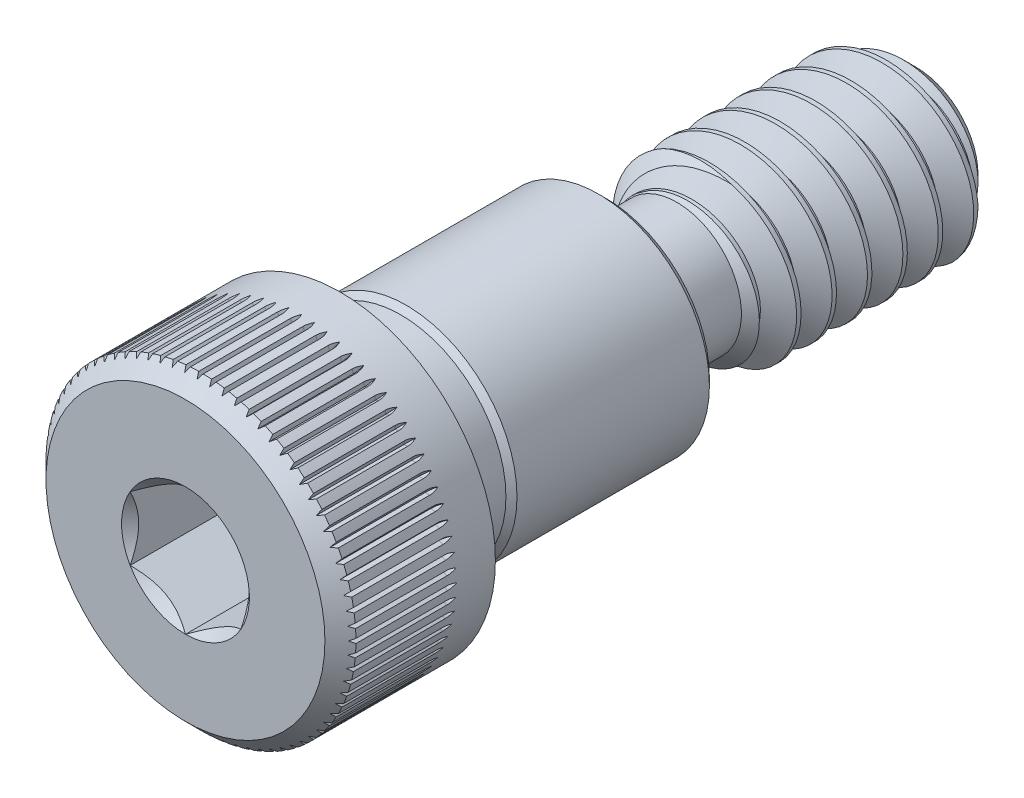
SolidWorks part; units mm, degrees
ref_plane "Front Plane" through (0, 0, 0) normal (0, 0, 1) x (1, 0, 0)
ref_plane "Top Plane" through (0, 0, 0) normal (0, 1, 0) x (1, 0, 0)
ref_plane "Right Plane" through (0, 0, 0) normal (1, 0, 0) x (0, 0, -1)
sketch "Sketch2" plane through (0, 0, 0) normal (1, 0, 0) x (0, 0, -1)
  line L0 (-13.0969, 0) -> (13.0969, 0) construction
  line L1 (-13.0969, 0) -> (-13.0969, 5.5563)
  line L2 (-13.0969, 5.5563) -> (-7.5406, 5.5563)
  line L3 (-7.5406, 5.5563) -> (-7.5406, 3.9688)
  line L4 (-7.5406, 3.9688) -> (1.9844, 3.9688)
  line L5 (1.9844, 3.175) -> (13.0969, 3.175)
  line L6 (13.0969, 3.175) -> (13.0969, 0)
  line L7 (13.0175, 3.3125) -> (13.6525, 2.2126) construction
  line L8 (13.6525, 2.2126) -> (14.2875, 3.3125) construction
  line L9 (14.2875, 3.3125) -> (13.0175, 3.3125) construction
  line L10 (13.0969, 3.175) -> (14.2081, 3.175) construction
  line L11 (13.6525, 3.3125) -> (13.6525, 3.175) construction
  line L12 (13.6525, 3.175) -> (13.6525, 2.3501) construction
  line L13 (13.6525, 2.3501) -> (13.6525, 2.2126) construction
  line L14 (13.5731, 2.3501) -> (13.7319, 2.3501)
  line L15 (13.0572, 3.2437) -> (14.2478, 3.2437)
  line L16 (13.7319, 2.3501) -> (14.2478, 3.2437)
  line L17 (13.5731, 2.3501) -> (13.0572, 3.2437)
  line L18 (13.0969, 0) -> (13.0969, -3.175) construction
  line L19 (1.9844, -3.9688) -> (1.9844, 0) construction
  line L20 (1.9844, 0) -> (1.9844, 3.9688) construction
  line L21 (-13.0969, 0) -> (-13.0969, -5.5563) construction
  point P11 (-5.1784, 3.9688)
  point P12 (9.9219, -3.175)
  point P22 (13.6525, 3.2437)
  point P23 (1.4287, 0)
  point P25 (-1.4287, 0)
  point P26 (-7.5406, -5.5563)
  point P29 (1.9844, -3.9688)
  dimension "Head Height" = 5.5562
  dimension "Shoulder Diameter" = 7.9375
  dimension "Screw Size Decimal Equivalent" = 6.35
  dimension "Thread Length" = 11.1125
  dimension "Head Diameter" = 11.1125
  dimension "Undercut Length" = 2.3622
  dimension "Pitch" = 1.27
  dimension "D2" = 0.1588
  dimension "D1" = 3.175
  dimension "D3" = 11.6681
  dimension "D4" = 11.6681
  dimension "Shoulder Length" = 9.525
sketch "Sketch3" plane through (0, 0, 0) normal (0, 0, 1) x (1, 0, 0)
  line L1 (0, 2.2914) -> (-1.9844, 1.1457)
  line L2 (-1.9844, 1.1457) -> (-1.9844, -1.1457)
  line L3 (-1.9844, -1.1457) -> (0, -2.2914)
  line L4 (0, -2.2914) -> (1.9844, -1.1457)
  line L5 (1.9844, -1.1457) -> (1.9844, 1.1457)
  line L6 (1.9844, 1.1457) -> (0, 2.2914)
  circle A0 centre (0, 0) radius 1.9844 construction
  dimension "Drive Size" = 3.9688
sketch "Sketch4" plane through (0, 0, 0) normal (1, 0, 0) x (0, 0, -1)
  line L0 (-7.5406, 5.5563) -> (-12.5412, 5.5562)
  line L1 (-12.5412, 5.5562) -> (-13.0969, 5.0006)
  line L2 (-7.5406, 5.5563) -> (-7.5406, 3.9688)
  line L3 (-7.5406, 3.9688) -> (-7.3422, 3.7703)
  line L4 (-7.3422, 3.7703) -> (-5.3769, 3.7703)
  line L5 (-5.3769, 3.7703) -> (-5.1784, 3.9688)
  line L6 (-7.5406, 3.9688) -> (1.9844, 3.9688) construction
  line L7 (-13.0969, 0) -> (13.0969, 0) construction
  line L8 (-5.1784, 3.9688) -> (1.7198, 3.9688)
  line L9 (1.7198, 3.9688) -> (1.9844, 3.7042)
  line L10 (1.9844, 3.7042) -> (1.9844, 0)
  line L11 (1.9844, 3.9688) -> (1.9844, 3.7042) construction
  line L12 (1.9844, 3.7042) -> (1.9844, 3.4396) construction
  line L13 (1.9844, 3.4396) -> (1.9844, 3.175) construction
  line L14 (-13.0969, 5.0006) -> (-13.0969, 0)
  line L15 (-13.0969, 5.5563) -> (-7.5406, 5.5563) construction
  line L16 (-13.0969, 0) -> (1.9844, 0)
  dimension "D1" = 45
  dimension "D2" = 7.5406
  dimension "D3" = 45
  dimension "D4" = 45
  dimension "D5" = 10.0012
revolve "Revolve1" add sketch "Sketch4" angle 360 about L16
sketch "Sketch5" plane through (0, 0, 13.0969) normal (0, 0, 1) x (1, 0, 0)
  line L0 (1.9844, 1.1457) -> (0, 2.2914) construction
  line L1 (1.9844, -1.1457) -> (1.9844, 1.1457) construction
  line L2 (0, -2.2914) -> (1.9844, -1.1457) construction
  line L3 (-1.9844, -1.1457) -> (0, -2.2914) construction
  line L4 (-1.9844, 1.1457) -> (-1.9844, -1.1457) construction
  line L5 (0, 2.2914) -> (-1.9844, 1.1457) construction
  line L6 (1.9844, 1.1457) -> (0, 2.2914)
  line L7 (1.9844, -1.1457) -> (1.9844, 1.1457)
  line L8 (0, -2.2914) -> (1.9844, -1.1457)
  line L9 (-1.9844, -1.1457) -> (0, -2.2914)
  line L10 (-1.9844, 1.1457) -> (-1.9844, -1.1457)
  line L11 (0, 2.2914) -> (-1.9844, 1.1457)
extrude "Cut-Extrude1" cut sketch "Sketch5" against normal blind 4.1672
sketch "Sketch6" plane through (0, 0, 13.0969) normal (0, 0, 1) x (1, 0, 0)
  circle A0 centre (0, 0) radius 2.2914
extrude "Cut-Extrude4" cut sketch "Sketch6" against normal blind 4.1672 draft 45
sketch "Sketch7" plane through (0, 0, 0) normal (1, 0, 0) x (0, 0, -1)
  line L0 (1.9844, 3.175) -> (12.1444, 3.175)
  line L1 (1.9844, 3.175) -> (13.0969, 3.175) construction
  line L2 (12.1444, 3.175) -> (13.0969, 2.2225)
  line L3 (13.0969, 3.175) -> (13.0969, 0) construction
  line L4 (13.0969, 2.2225) -> (13.0969, 0)
  line L5 (13.0969, 0) -> (1.9844, 0)
  line L6 (1.9844, -3.7042) -> (1.9844, 3.7042) construction
  line L7 (1.9844, 0) -> (1.9844, 3.175)
  dimension "D1" = 45
  dimension "D2" = 0.9525
revolve "Revolve2" add sketch "Sketch7" angle 360 about L5
sketch "Sketch10" plane through (0, 0, 0) normal (1, 0, 0) x (0, 0, -1)
  line L0 (2.848, 2.3114) -> (4.5244, 2.3114)
  line L1 (4.5244, 2.3114) -> (6.1817, 3.9688)
  line L2 (6.1817, 3.9688) -> (1.9844, 3.9688)
  line L3 (1.9844, 3.9688) -> (1.9844, 3.175)
  line L4 (1.9844, -3.7042) -> (1.9844, 3.7042) construction
  line L5 (13.0969, 0) -> (1.9844, 0) construction
  line L6 (-13.0969, 0) -> (13.0969, 0) construction
  arc A0 (1.9844, 3.175) -> (2.848, 2.3114) centre (2.848, 3.175) ccw
  dimension "Flat OD" = 4.6228
  dimension "Flat" = 2.54
  dimension "D3" = 45
revolve "Cut-Revolve1" cut sketch "Sketch10" angle 360 about L5
sketch "Sketch8" plane through (0, 0, -13.0969) normal (0, 0, -1) x (-1, 0, 0)
  circle A0 centre (0, 0) radius 3.175 construction
  circle A1 centre (0, 0) radius 3.175
curve "Helix/Spiral1" pitch 1.27 height 12.3825 radius 3.175 centre (0, 0, -13.0969) axis (0, 0, 1) start towards (0, 1, 0)
sketch "Sketch9" plane through (0, 0, 0) normal (1, 0, 0) x (0, 0, -1)
  line L0 (13.5731, 2.3501) -> (13.7319, 2.3501) construction
  line L1 (13.7319, 2.3501) -> (14.2478, 3.2437) construction
  line L2 (13.0572, 3.2437) -> (14.2478, 3.2437) construction
  line L3 (13.5731, 2.3501) -> (13.0572, 3.2437) construction
  line L4 (13.5731, 2.3501) -> (13.7319, 2.3501)
  line L5 (13.7319, 2.3501) -> (14.2478, 3.2437)
  line L6 (13.0572, 3.2437) -> (14.2478, 3.2437)
  line L7 (13.5731, 2.3501) -> (13.0572, 3.2437)
ref_plane "Plane1" through (0, 0, -4.5244) normal (0, 0, 1) x (1, 0, 0)
split "Split1" trim tools "Plane1" bodies to split 138 resulting bodies 139 140
sweep "Cut-Sweep1" cut profiles "Sketch9" path "Helix/Spiral1" align with end faces yes
combine bodies "Combine1" operation type add bodies to combine 141 139
sketch "Sketch11" plane through (0, 0, 13.0969) normal (0, 0, 1) x (1, 0, 0)
  line L0 (-0.0802, 5.5562) -> (0.0802, 5.5562)
  line L1 (0.0802, 5.5562) -> (0, 5.4173)
  line L2 (0, 0) -> (0, 5.5563) construction
  line L3 (0, 5.4173) -> (-0.0802, 5.5562)
  line L4 (0, 0) -> (5.5562, 0) construction
  circle A0 centre (0, 0) radius 5.5562 construction
  point P6 (0, 5.5562)
  dimension "D1" = 10.8347
  dimension "D2" = 60
  dimension "D3" = 0.1604
sketch "Sketch12" plane through (0, 0, 0) normal (1, 0, 0) x (0, 0, -1)
  line L0 (-13.0969, 5.4173) -> (-9.265, 5.4173)
  line L1 (-8.7908, 5.8916) -> (-8.7908, 5.5563) construction
  line L2 (-13.0969, 5.5563) -> (-7.5406, 5.5563) construction
  arc A0 (-9.265, 5.4173) -> (-8.7908, 5.8916) centre (-9.265, 5.8916) ccw
  point P11 (-8.9297, 5.5563)
  dimension "D1" = 1.3891
sweep "Cut-Sweep2" cut profiles "Sketch11" path "Sketch12"
pattern_circular "CirPattern1" count 76 over 360 about axis through (0, 0, 13.0969) along (0, 0, -1) of "Cut-Sweep2"
equation "\"D2@Sketch2\" = \"Pitch@Sketch2\" / 8"
equation "\"D1@Sketch2\"=\"Pitch@Sketch2\"*2.5"
equation "\"D2@Sketch4\"=\"Shoulder Diameter@Sketch2\"*0.95"
equation "\"D5@Sketch4\"=\"Head Diameter@Sketch2\"*0.9"
equation "\"D1@Cut-Extrude1\"=\"Head Height@Sketch2\"*0.75"
equation "\"D1@Cut-Extrude4\"=\"D1@Cut-Extrude1\""
equation "\"D2@Sketch7\"=\"pitch@sketch2\"*0.75"
equation "\"D3@Helix/Spiral1\"=\"Thread Length@Sketch2\"+\"Pitch@Sketch2\""
equation "\"D4@Helix/Spiral1\"=\"Pitch@Sketch2\""
equation "\"D1@Sketch11\"=\"Head Diameter@Sketch2\"*0.975"
equation "\"D1@Sketch12\"=\"Head Height@Sketch2\"*0.25"
equation "\"D1@CirPattern1\"=\"Head Diameter@Sketch2\" * 3.14 / \"D3@Sketch11\" * 0.35"
equation "\"D3@Sketch2\"=\"Thread Length@Sketch2\"*1.05"
equation "\"D4@Sketch2\"=\"D3@Sketch2\""
